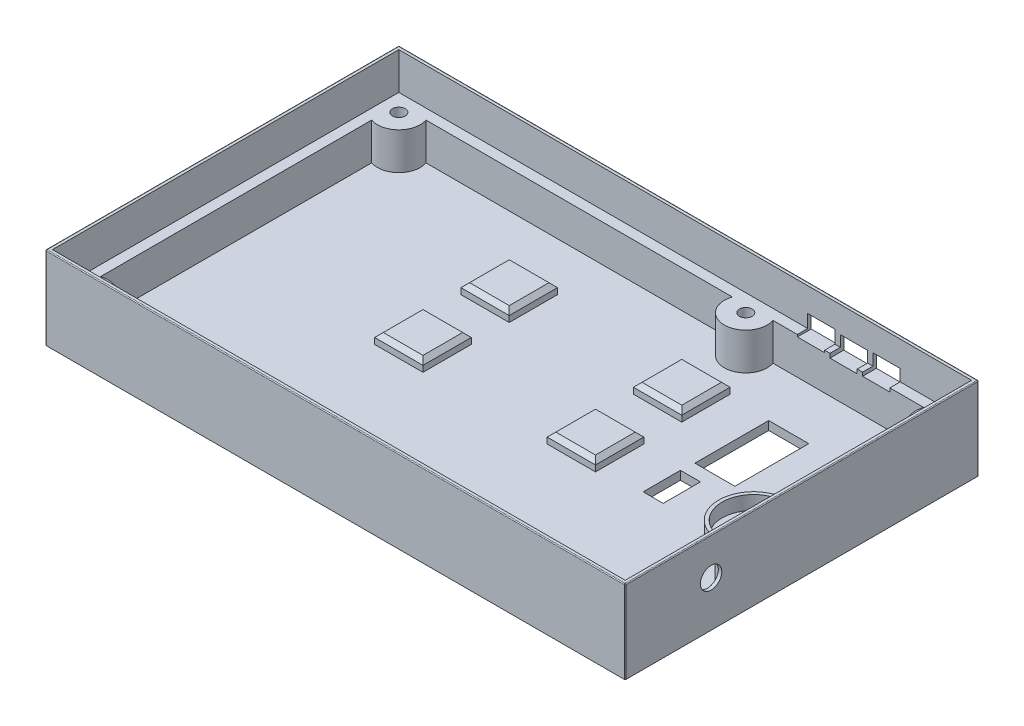
SolidWorks part; units mm, degrees
ref_plane "Front Plane" through (0, 0, 0) normal (0, 0, 1) x (1, 0, 0)
ref_plane "Top Plane" through (0, 0, 0) normal (0, 1, 0) x (1, 0, 0)
ref_plane "Right Plane" through (0, 0, 0) normal (1, 0, 0) x (0, 0, -1)
sketch "BaseSketch1" plane through (0, 0, 0) normal (0, 1, 0) x (1, 0, 0)
  line L1 (0, 0) -> (168, 0)
  line L2 (0, 0) -> (0, 102.4)
  line L3 (0, 102.4) -> (168, 102.4)
  line L4 (168, 0) -> (168, 102.4)
  line L5 (126.2, 83.4) -> (137.8, 83.4)
  line L6 (126.2, 83.4) -> (126.2, 62)
  line L7 (126.2, 62) -> (137.8, 62)
  line L8 (137.8, 83.4) -> (137.8, 62)
  line L9 (125.9, 47.31) -> (131.7, 47.31)
  line L10 (125.9, 47.31) -> (125.9, 58.11)
  line L11 (125.9, 58.11) -> (131.7, 58.11)
  line L12 (131.7, 47.31) -> (131.7, 58.11)
  circle A0 centre (57, 77.4) radius 2
  circle A1 centre (107, 77.4) radius 2
  circle A2 centre (57, 52.4) radius 2
  circle A3 centre (107, 52.4) radius 2
  circle A4 centre (6, 96.4) radius 1.85
  circle A5 centre (6, 6) radius 1.85
  circle A6 centre (162, 6) radius 1.85
  circle A7 centre (162, 96.4) radius 1.85
  circle A8 centre (106.55, 96.4) radius 1.85
  dimension "D16" = 3.7
  dimension "D7" = 4
  dimension "D1" = 102.4
  dimension "D2" = 168
  dimension "D3" = 50
  dimension "D4" = 25
  dimension "D6" = 25
  dimension "D8" = 21.4
  dimension "D9" = 11.6
  dimension "D10" = 40.4
  dimension "D12" = 5.8
  dimension "D13" = 10.8
  dimension "D15" = 55.09
  dimension "D17" = 6
  dimension "D18" = 6
  dimension "D19" = 6
  dimension "D20" = 6
  dimension "D5" = 57
  dimension "D11" = 41.8
  dimension "D14" = 42.1
  dimension "D21" = 106.55
extrude "BaseBoss-Extrude1" add sketch "BaseSketch1" along normal blind 2.5
sketch "Sketch2" plane through (0, 2.5, 0) normal (0, 1, 0) x (1, 0, 0)
  line L1 (0, 0) -> (168, 0)
  line L2 (0, 0) -> (0, 102.4)
  line L3 (0, 102.4) -> (168, 102.4)
  line L4 (168, 0) -> (168, 102.4)
  line L5 (4, 98.4) -> (164, 98.4)
  line L6 (4, 98.4) -> (4, 4)
  line L7 (4, 4) -> (164, 4)
  line L8 (164, 98.4) -> (164, 4)
  dimension "D1" = 4
  dimension "D2" = 4
  dimension "D3" = 4
  dimension "D4" = 4
extrude "WallBoss-Extrude2" add sketch "Sketch2" along normal blind 21.5
sketch "Sketch3" plane through (0, 2.5, 0) normal (0, 1, 0) x (1, 0, 0)
  line L1 (50, 84.4) -> (64, 84.4)
  line L2 (50, 84.4) -> (50, 70.4)
  line L3 (50, 70.4) -> (64, 70.4)
  line L4 (64, 84.4) -> (64, 70.4)
  line L5 (50, 84.4) -> (64, 70.4) construction
  line L6 (50, 70.4) -> (64, 84.4) construction
  line L7 (50, 59.4) -> (64, 59.4)
  line L8 (50, 59.4) -> (50, 45.4)
  line L9 (50, 45.4) -> (64, 45.4)
  line L10 (64, 59.4) -> (64, 45.4)
  line L11 (50, 59.4) -> (64, 45.4) construction
  line L12 (50, 45.4) -> (64, 59.4) construction
  line L13 (100, 84.4) -> (114, 84.4)
  line L14 (100, 84.4) -> (100, 70.4)
  line L15 (100, 70.4) -> (114, 70.4)
  line L16 (114, 84.4) -> (114, 70.4)
  line L17 (100, 84.4) -> (114, 70.4) construction
  line L18 (100, 70.4) -> (114, 84.4) construction
  line L19 (100, 59.4) -> (114, 59.4)
  line L20 (100, 59.4) -> (100, 45.4)
  line L21 (100, 45.4) -> (114, 45.4)
  line L22 (114, 59.4) -> (114, 45.4)
  line L23 (100, 59.4) -> (114, 45.4) construction
  line L24 (100, 45.4) -> (114, 59.4) construction
  point P0 (57, 77.4)
  point P6 (57, 52.4)
  point P12 (107, 77.4)
  point P18 (107, 52.4)
  dimension "D1" = 14
extrude "MountHoleBoss-Extrude3" add sketch "Sketch3" along normal blind 3
chamfer "MountHoleBossChamfer3" distance 1.25 angle 45 16 edges at (57, 5.5, -59.4) (107, 5.5, -59.4) (107, 5.5, -84.4) (57, 5.5, -84.4) (50, 5.5, -52.4) (100, 5.5, -52.4) (100, 5.5, -77.4) (50, 5.5, -77.4) (64, 5.5, -52.4) (114, 5.5, -52.4) (114, 5.5, -77.4) (64, 5.5, -77.4) (57, 5.5, -70.4) (57, 5.5, -45.4) (107, 5.5, -45.4) (107, 5.5, -70.4)
sketch "HDMI7MountHolesSketch8" plane through (0, 2.5, 0) normal (0, 1, 0) x (1, 0, 0)
  line L0 (164, 98.4) -> (4, 98.4) construction
  line L1 (4, 98.4) -> (4, 4) construction
  line L2 (4, 90.5243) -> (4, 98.4)
  line L3 (4, 98.4) -> (11.8757, 98.4)
  line L4 (164, 4) -> (164, 98.4) construction
  line L5 (4, 4) -> (164, 4) construction
  line L6 (4, 98.4) -> (4, 4) construction
  line L7 (4, 4) -> (164, 4) construction
  line L8 (156.1243, 98.4) -> (164, 98.4)
  line L9 (164, 98.4) -> (164, 90.5243)
  line L10 (156.1243, 4) -> (164, 4)
  line L11 (164, 4) -> (164, 11.8757)
  line L12 (11.8757, 4) -> (4, 4)
  line L13 (4, 4) -> (4, 11.8757)
  line L14 (100.6743, 98.4) -> (112.4257, 98.4)
  arc A0 (11.8757, 98.4) -> (4, 90.5243) centre (6, 96.4) cw
  circle A1 centre (6, 96.4) radius 1.85
  circle A2 centre (6, 96.4) radius 1.85 construction
  circle A3 centre (162, 96.4) radius 1.85
  circle A4 centre (162, 96.4) radius 1.85 construction
  arc A5 (164, 90.5243) -> (156.1243, 98.4) centre (162, 96.4) cw
  arc A6 (164, 11.8757) -> (156.1243, 4) centre (162, 6) ccw
  arc A7 (4, 11.8757) -> (11.8757, 4) centre (6, 6) cw
  circle A8 centre (162, 6) radius 1.85
  circle A9 centre (162, 6) radius 1.85 construction
  circle A10 centre (6, 6) radius 1.85
  circle A11 centre (6, 6) radius 1.85 construction
  arc A12 (100.6743, 98.4) -> (112.4257, 98.4) centre (106.55, 96.4) ccw
  circle A13 centre (106.55, 96.4) radius 1.85
  circle A14 centre (106.55, 96.4) radius 1.85 construction
extrude "HDMI7MountHolesBoss-Extrude4" add sketch "HDMI7MountHolesSketch8" along normal blind 10.75
sketch "DisplayButtonsSketch9" plane through (0, 0, -102.4) normal (0, 0, -1) x (-1, 0, 0)
  line L0 (-168, 24) -> (0, 24) construction
  line L1 (-146.3, 16.61) -> (-138.4, 16.61)
  line L2 (-146.3, 16.61) -> (-146.3, 12.21)
  line L3 (-146.3, 12.21) -> (-138.4, 12.21)
  line L4 (-138.4, 16.61) -> (-138.4, 12.21)
  line L5 (-136.85, 16.4439) -> (-128.95, 16.4439)
  line L6 (-136.85, 16.4439) -> (-136.85, 12.0439)
  line L7 (-136.85, 12.0439) -> (-128.95, 12.0439)
  line L8 (-128.95, 16.4439) -> (-128.95, 12.0439)
  line L9 (-127.4, 17.0239) -> (-119.5, 17.0239)
  line L10 (-127.4, 17.0239) -> (-127.4, 12.6239)
  line L11 (-127.4, 12.6239) -> (-119.5, 12.6239)
  line L12 (-119.5, 17.0239) -> (-119.5, 12.6239)
  line L13 (-168, 24) -> (-168, 0) construction
  dimension "D1" = 7.9
  dimension "D3" = 11.79
  dimension "D4" = 29.6
  dimension "D2" = 4.4
  dimension "D6" = 1.55
  dimension "D5" = 1.55
  dimension "D7" = 48.5
  dimension "D8" = 7.9
  dimension "D9" = 7.9
extrude "DisplayButtonsCut-Extrude1" cut sketch "DisplayButtonsSketch9" against normal up to next
sketch "AudioConnectorSketch10" plane through (168, 0, 0) normal (1, 0, 0) x (0, 0, -1)
  line L0 (0, 24) -> (102.4, 24) construction
  line L1 (0, 24) -> (0, 0) construction
  circle A0 centre (24.9, 13.2) radius 3.1
  dimension "D1" = 6.2
  dimension "D2" = 10.8
  dimension "D3" = 24.9
extrude "AudioConnectorCut-Extrude2" cut sketch "AudioConnectorSketch10" against normal up to next
sketch "M3BoreSketch11" plane through (0, 0, 0) normal (0, -1, 0) x (1, 0, 0)
  circle A0 centre (6, -6) radius 2.85
  circle A1 centre (162, -6) radius 2.85
  circle A2 centre (162, -96.4) radius 2.85
  circle A3 centre (6, -96.4) radius 2.85
  circle A4 centre (106.55, -96.4) radius 2.85
  dimension "D1" = 5.7
extrude "M3BoreCut-Extrude3" cut sketch "M3BoreSketch11" against normal blind 3
sketch "UpperThinWallSketch4" plane through (0, 24, 0) normal (0, 1, 0) x (1, 0, 0)
  line L1 (4, 98.4) -> (164, 98.4)
  line L2 (4, 98.4) -> (4, 4)
  line L3 (4, 4) -> (164, 4)
  line L4 (164, 98.4) -> (164, 4)
  line L6 (167, 1) -> (1, 1)
  line L7 (167, 1) -> (167, 101.4)
  line L8 (167, 101.4) -> (1, 101.4)
  line L9 (1, 1) -> (1, 101.4)
  dimension "D1" = 3
  dimension "D2" = 3
  dimension "D3" = 3
  dimension "D4" = 3
extrude "UpperThinWallCut-Extrude1" cut sketch "UpperThinWallSketch4" against normal blind 10.75
sketch "HDMI7AudioConnectorKnotchSketch5" plane through (0, 13.25, 0) normal (0, 1, 0) x (1, 0, 0)
  line L0 (164, 27.9996) -> (167, 27.9996) construction
  line L1 (164, 29.9996) -> (167, 29.9996)
  line L2 (164, 29.9996) -> (164, 19.8004)
  line L3 (164, 19.8004) -> (167, 19.8004)
  line L4 (167, 29.9996) -> (167, 19.8004)
  line L6 (167, 1) -> (167, 21.8004) construction
  line L7 (164, 11.8757) -> (164, 90.5243) construction
  line L8 (167, 21.8004) -> (164, 21.8004) construction
  dimension "D1" = 2
  dimension "D2" = 2
extrude "HDMI7AudioConnectorKnotchCut-Extrude2" cut sketch "HDMI7AudioConnectorKnotchSketch5" against normal blind 8.2
fillet "TopFillet1" radius 0.25 4 edges at (168, 24, -51.2) (84, 24, 0) (0, 24, -51.2) (84, 24, -102.4)
fillet "CornerFillet2" radius 0.25 8 edges at (0.0732, 23.9268, -0.0732) (0.0732, 23.9268, -102.3268) (167.9268, 23.9268, -0.0732) (0, 11.875, 0) (0, 11.875, -102.4) (168, 11.875, 0) (167.9268, 23.9268, -102.3268) (168, 11.875, -102.4)
sketch "SpeakerHoleSketch4" plane through (0, 2.5, 0) normal (0, 1, 0) x (1, 0, 0)
  line L0 (0.25, 102.4) -> (167.75, 102.4) construction
  line L1 (168, 102.15) -> (168, 0.25) construction
  circle A0 centre (153, 52.2) radius 6.75
  dimension "D1" = 13.5
  dimension "D2" = 50.2
  dimension "D3" = 15
extrude "SpeaerHoleCut-Extrude1" cut sketch "SpeakerHoleSketch4" against normal through all
sketch "SpeakerHolderSketch5" plane through (0, 2.5, 0) normal (0, 1, 0) x (1, 0, 0)
  line L2 (50, 59.4) -> (50, 45.4) construction
  line L3 (50, 45.4) -> (64, 45.4) construction
  circle A0 centre (153, 52.2) radius 9.1
  circle A1 centre (153, 52.2) radius 10.1
  dimension "D1" = 18.2
  dimension "D2" = 20.2
extrude "SpeakerHolderBoss-Extrude1" add sketch "SpeakerHolderSketch5" along normal blind 4
equation "\"HDMI7CaseWidth\"= 100mm + .4mm'Spec Add .4mm as width was slightly to tight"
equation "\"D1@BaseSketch1\" = \"HDMI7CaseWidth\" + \"HDMI7OuterCaseWallThickness\" * 2"
equation "\"HDMI7CaseLength\"= 165mm + 1mm'Spec Add 1mm as length did not fit"
equation "\"HDMI7CaseHeight\"= 24mm"
equation "\"HDMI7Height\"= 10.75mm'Spec"
equation "\"HDMI7MountingHoleOffset\"= 5mm'Spec"
equation "\"M3ScrewDiameter\"= 3mm + .5'Spec Add .5mm for easy screw insert"
equation "\"D2@BaseSketch1\"= \"HDMI7CaseLength\" + \"HDMI7OuterCaseWallThickness\" * 2"
equation "\"HDMI7BaseThickness\"= 2.5mm"
equation "\"HDMIMountHoleXDistance\"=50"
equation "\"D3@BaseSketch1\"=\"HDMIMountHoleXDistance\""
equation "\"HDMIMountHoleYDistance\"=25"
equation "\"D10@BaseSketch1\"=\"HDMI7HDMIConnectorDistanceFromTop\" + \"HDMI7OuterCaseWallThickness\" + \"HDMI7SpaceAroundAConnector\""
equation "\"D6@BaseSketch1\" = \"HDMI7MountingBracketOffsetFromTop\" + \"HDMI7OuterCaseWallThickness\""
equation "\"D15@BaseSketch1\"=\"HDMI7USBCConnectorDistanceFromTop\" + \"HDMI7OuterCaseWallThickness\" + \"HDMI7SpaceAroundAConnector\"*2"
equation "\"D1@BaseBoss-Extrude1\" = \"HDMI7BaseThickness\""
equation "\"D1@Sketch2\"=\"HDMI7OuterCaseWallThickness\" + \"HDMI7InnerCaseWallThickness\""
equation "\"D2@Sketch2\"=\"HDMI7OuterCaseWallThickness\" + \"HDMI7InnerCaseWallThickness\""
equation "\"D3@Sketch2\"=\"HDMI7OuterCaseWallThickness\" +\"HDMI7InnerCaseWallThickness\""
equation "\"D4@Sketch2\"=\"HDMI7OuterCaseWallThickness\" + \"HDMI7InnerCaseWallThickness\""
equation "\"D1@WallBoss-Extrude2\" = \"HDMI7CaseHeight\" - \"HDMI7BaseThickness\""
equation "\"D1@Sketch3\"=\"M3ScrewDiameter\"*4"
equation "\"D1@MountHoleBoss-Extrude3\"=\"M3ButtonHeadLength\""
equation "\"D16@BaseSketch1\"=\"M3ScrewDiameter\" +.2"
equation "\"D18@BaseSketch1\"=\"HDMI7MountingHoleOffset\" + \"HDMI7OuterCaseWallThickness\""
equation "\"D17@BaseSketch1\"=\"HDMI7MountingHoleOffset\"+\"HDMI7OuterCaseWallThickness\""
equation "\"D19@BaseSketch1\"=\"HDMI7MountingHoleOffset\"+\"HDMI7OuterCaseWallThickness\""
equation "\"D20@BaseSketch1\"=\"HDMI7MountingHoleOffset\"+\"HDMI7OuterCaseWallThickness\""
equation "\"D1@HDMI7MountHolesBoss-Extrude4\"=\"HDMI7CaseHeight\" - \"HDMI7Height\" - \"HDMI7BaseThickness\""
equation "\"D5@BaseSketch1\" = \"HDMI7MountingBracketOffsetFromEdge\" + \"HDMI7OuterCaseWallThickness\""
equation "\"D4@DisplayButtonsSketch9\"=\"HDMI7DisplayButtonDistanceFromNearestEdge\" + \"HDMI7OuterCaseWallThickness\" + \"HDMI7SpaceAroundAConnector\""
equation "\"D2@AudioConnectorSketch10\"= \"HDMI7AudioConnectorDistanceFromTop\" - \"HDMI7AudioConnectorHoleDiameter\" / 2"
equation "\"D3@AudioConnectorSketch10\"= \"HDMI7AudioConnectorDistanceFromNearestEdge\" + \"HDMI7OuterCaseWallThickness\" - \"HDMI7AudioConnectorHoleDiameter\" / 2"
equation "\"M3ButtonHeadDiameter\"= 5.5mm'Spec"
equation "\"M3ButtonHeadLength\"= 3mm'Spec"
equation "\"D1@M3BoreSketch11\"=\"M3ButtonHeadDiameter\" + .2mm"
equation "\"D1@M3BoreCut-Extrude3\"=\"M3ButtonHeadLength\""
equation "\"HDMI7InnerCaseWallThickness\"= 3mm"
equation "\"HDMI7OuterCaseWallThickness\"= 1mm"
equation "\"D1@UpperThinWallSketch4\" = \"HDMI7InnerCaseWallThickness\""
equation "\"D2@UpperThinWallSketch4\" = \"HDMI7InnerCaseWallThickness\""
equation "\"D3@UpperThinWallSketch4\" = \"HDMI7InnerCaseWallThickness\""
equation "\"D4@UpperThinWallSketch4\" = \"HDMI7InnerCaseWallThickness\""
equation "\"D1@UpperThinWallCut-Extrude1\" = \"HDMI7Height\""
equation "\"HDMI7AudioConnectorHoleDiameter\"= 6mm + \"HDMI7SpaceAroundAConnector\" * 2"
equation "\"D1@AudioConnectorSketch10\"=\"HDMI7AudioConnectorHoleDiameter\""
equation "\"HDMI7AudioConnectorDistanceFromNearestEdge\"= 27mm"
equation "\"HDMI7AudioConnectorDistanceFromTop\"= 13.8mm + \"HDMI7SpaceAroundAConnector\""
equation "\"D1@HDMI7AudioConnectorKnotchCut-Extrude2\"=\"HDMI7AudioConnectorHoleDiameter\" + 2mm"
equation "\"HDMI7DisplayButtonDistanceFromTop\"=11.69"
equation "\"D3@DisplayButtonsSketch9\"=\"HDMI7DisplayButtonDistanceFromTop\" + \"HDMI7SpaceAroundAConnector\""
equation "\"HDMI7DisplayButtonHeight\"= 4.2mm"
equation "\"D2@DisplayButtonsSketch9\"=\"HDMI7DisplayButtonHeight\" + \"HDMI7SpaceAroundAConnector\"*2"
equation "\"HDMI7DisplayButtonWidth\"= 7.7mm"
equation "\"D1@DisplayButtonsSketch9\"=\"HDMI7DisplayButtonWidth\" + \"HDMI7SpaceAroundAConnector\" * 2"
equation "\"HDMI7DisplayButtonDistanceFromNearestEdge\"= 28.5mm"
equation "\"HDMI7DisplayButtonOffsetBetweenEach\"=1.75"
equation "\"D6@DisplayButtonsSketch9\"=\"HDMI7DisplayButtonOffsetBetweenEach\" - \"HDMI7SpaceAroundAConnector\"*2"
equation "\"D5@DisplayButtonsSketch9\"=\"HDMI7DisplayButtonOffsetBetweenEach\" - \"HDMI7SpaceAroundAConnector\"*2"
equation "\"HDMI7HDMIConnectorLength\"= 21.2mm'Measured"
equation "\"D8@BaseSketch1\"=\"HDMI7HDMIConnectorLength\" + \"HDMI7SpaceAroundAConnector\"*2"
equation "\"HDMI7HDMIConnectorWidth\"= 11.5mm'Measured"
equation "\"D9@BaseSketch1\"=\"HDMI7HDMIConnectorWidth\" + \"HDMI7SpaceAroundAConnector\""
equation "\"HDMI7USBConnectorLength\"= 10.7mm'Measured"
equation "\"D13@BaseSketch1\"=\"HDMI7USBConnectorLength\" + \"HDMI7SpaceAroundAConnector\""
equation "\"HDMI7USBCConnectorWidth\"= 5.7mm'Measured"
equation "\"D12@BaseSketch1\"=\"HDMI7USBCConnectorWidth\" + \"HDMI7SpaceAroundAConnector\""
equation "\"HDMI7HDMIConnectorDistanceFromNearestSide\"= 38.7mm"
equation "\"HDMI7USBConnectorDistanceFromNearestSide\"= 39mm"
equation "\"D11@BaseSketch1\"=\"HDMI7HDMIConnectorDistanceFromNearestSide\" + \"HDMI7InnerCaseWallThickness\" + \"HDMI7SpaceAroundAConnector\""
equation "\"D14@BaseSketch1\"=\"HDMI7USBConnectorDistanceFromNearestSide\" +\"HDMI7InnerCaseWallThickness\" + \"HDMI7SpaceAroundAConnector\""
equation "\"HDMI7USBCConnectorDistanceFromTop\"= 53.89mm"
equation "\"HDMI7HDMIConnectorDistanceFromTop\"= 39.3mm"
equation "\"HDMI7MountingBracketOffsetFromEdge\"= 56mm"
equation "\"HDMI7MountingBracketOffsetFromTop\"= 24mm"
equation "\"HDMI7SpaceAroundAConnector\"= .1mm"
equation "\"D7@BaseSketch1\"= \"M3HeatInsertHoleDiameter\""
equation "\"D8@DisplayButtonsSketch9\"=\"HDMI7DisplayButtonWidth\" + \"HDMI7SpaceAroundAConnector\"*2"
equation "\"D9@DisplayButtonsSketch9\"=\"HDMI7DisplayButtonWidth\" + \"HDMI7SpaceAroundAConnector\"*2"
equation "\"HDMI7MidMouningHoleOffset\"=106.55"
equation "\"M3HeatInsertHoleDiameter\"= 4mm'Spec"
equation "\"SpeakerHoleDiameter\"= 13.5mm"
equation "\"D2@SpeakerHoleSketch4\" = \"HDMI7CaseWidth\" / 2"
equation "\"SpeakerDistanceFromNearestEdge\"= 15mm"
equation "\"D3@SpeakerHoleSketch4\" = \"SpeakerDistanceFromNearestEdge\""
equation "\"SpeakerDiameter\"= 18.2mm'Spec Add .2mm for Filament expansion"
equation "\"D1@SpeakerHolderSketch5\"=\"SpeakerDiameter\""
equation "\"D2@SpeakerHolderSketch5\"=\"SpeakerDiameter\" + 2mm"
equation "\"SpeakerDepth\"=4"
equation "\"D1@SpeakerHolderBoss-Extrude1\"=\"SpeakerDepth\""
equation "\"D21@BaseSketch1\"=\"HDMI7MidMouningHoleOffset\""
